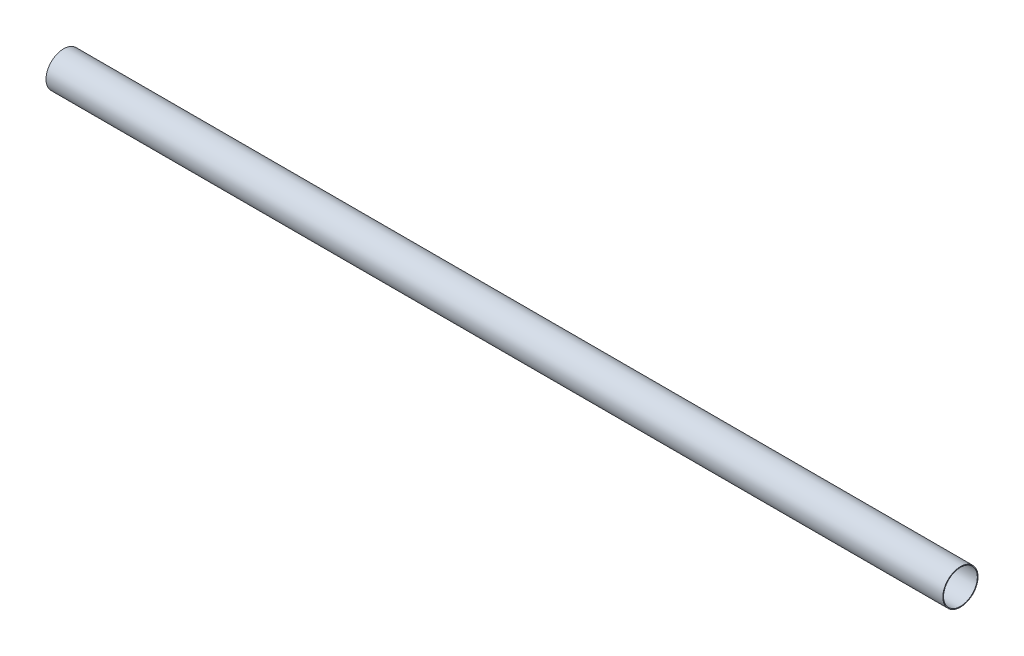
SolidWorks part; units mm, degrees
ref_plane "Front Plane" through (0, 0, 0) normal (0, 0, 1) x (1, 0, 0)
ref_plane "Top Plane" through (0, 0, 0) normal (0, 1, 0) x (1, 0, 0)
ref_plane "Right Plane" through (0, 0, 0) normal (1, 0, 0) x (0, 0, -1)
sketch "Leg_Sleeve Sketch" plane through (0, 0, 0) normal (0, 0, 1) x (1, 0, 0)
  line L0 (-3000, 0) -> (3000, 0) construction
  line L1 (500, 15.05) -> (1300, 15.05)
  line L2 (1300, 15.05) -> (1300, 15.7)
  line L3 (1300, 15.7) -> (500, 15.7)
  line L4 (500, 15.7) -> (500, 15.05)
revolve "Leg_Sleeve" add sketch "Leg_Sleeve Sketch" angle 360 about L0
ref_axis "Engine Axis" through (1340, 0, 0) along (-1, 0, 0)
